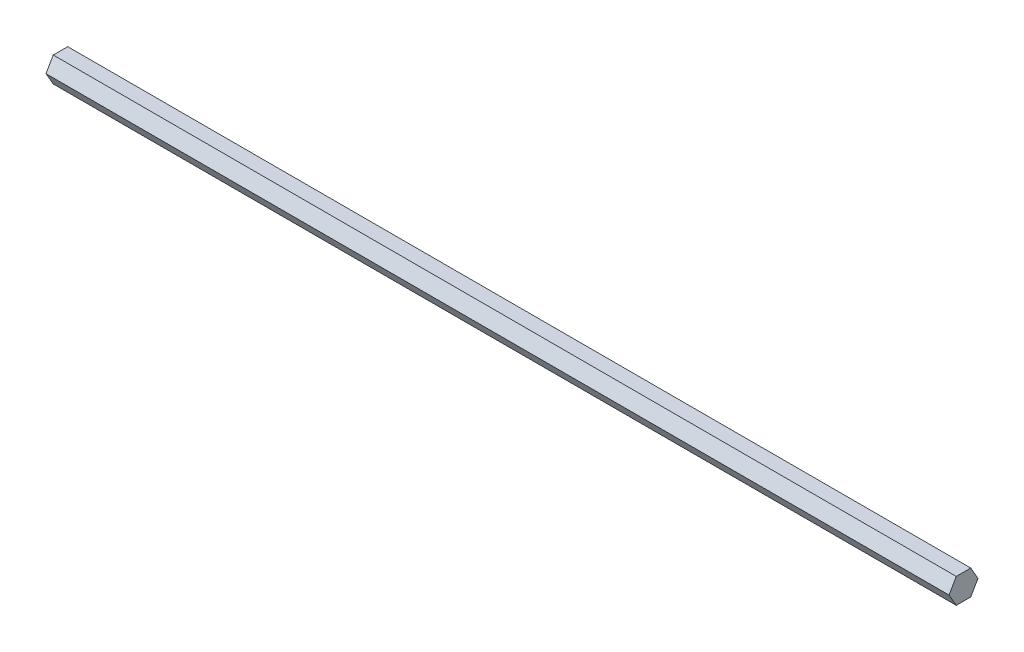
SolidWorks part; units mm, degrees
material "7075-T6 (SN)"
ref_plane "Front Plane" through (0, 0, 0) normal (0, 0, 1) x (1, 0, 0)
ref_plane "Top Plane" through (0, 0, 0) normal (0, 1, 0) x (1, 0, 0)
ref_plane "Right Plane" through (0, 0, 0) normal (1, 0, 0) x (0, 0, -1)
sketch "Sketch1" plane through (0, 0, 0) normal (1, 0, 0) x (0, 0, -1)
  line L1 (7.3323, 0) -> (3.6662, 6.35)
  line L2 (3.6662, 6.35) -> (-3.6662, 6.35)
  line L3 (-3.6662, 6.35) -> (-7.3323, 0)
  line L4 (-7.3323, 0) -> (-3.6662, -6.35)
  line L5 (-3.6662, -6.35) -> (3.6662, -6.35)
  line L6 (3.6662, -6.35) -> (7.3323, 0)
  circle A0 centre (0, 0) radius 6.35 construction
  dimension "D1" = 12.7
extrude "Boss-Extrude1" add sketch "Sketch1" along normal mid plane 457.2
ref_axis "Axis1" through (-230.505, 0, 0) along (1, 0, 0)
